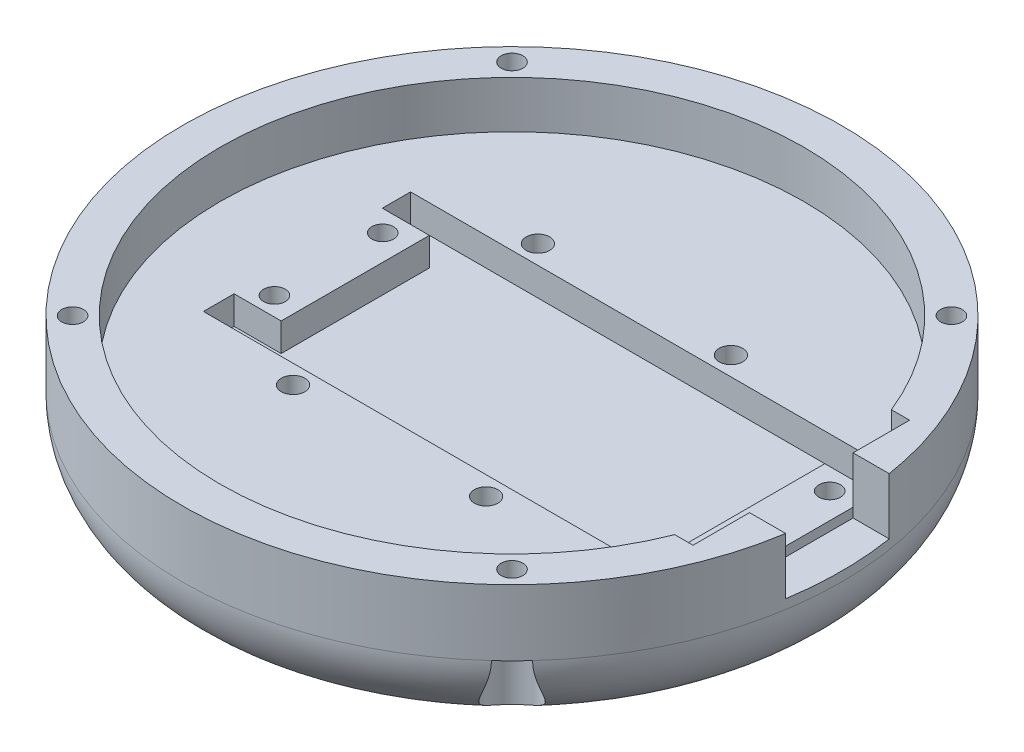
SolidWorks part; units mm, degrees
ref_plane "Front Plane" through (0, 0, 0) normal (0, 0, 1) x (1, 0, 0)
ref_plane "Top Plane" through (0, 0, 0) normal (0, 1, 0) x (1, 0, 0)
ref_plane "Right Plane" through (0, 0, 0) normal (1, 0, 0) x (0, 0, -1)
sketch "Sketch1" plane through (0, 0, 0) normal (0, 1, 0) x (1, 0, 0)
  circle A0 centre (0, 0) radius 35
  dimension "D1" = 70
extrude "Boss-Extrude1" add sketch "Sketch1" along normal blind 10
sketch "Sketch2" plane through (0, 10, 0) normal (0, 1, 0) x (1, 0, 0)
  line L0 (0, 0) -> (35, 0) construction
  line L1 (-21.7735, -11) -> (-21.7735, 11)
  line L2 (-21.7735, -11) -> (30.2265, -11)
  line L3 (-21.7735, 11) -> (30.2265, 11)
  line L4 (30.2265, -11) -> (30.2265, 11)
  line L5 (-21.7735, -11) -> (30.2265, 11) construction
  line L6 (-21.7735, 11) -> (30.2265, -11) construction
  line L7 (30.2265, 11) -> (33.2265, 11) construction
  line L8 (30.2265, 8) -> (25.2265, 8)
  line L9 (25.2265, 8) -> (25.2265, -8)
  line L10 (25.2265, -8) -> (30.2265, -8)
  line L11 (-21.7735, 8) -> (-16.7735, 8)
  line L12 (-16.7735, 8) -> (-16.7735, -7.7436)
  line L13 (-16.7735, -7.7436) -> (-21.7735, -7.7436)
  circle A0 centre (0, 0) radius 35 construction
  circle A1 centre (27.9931, 5.75) radius 1.15
  circle A2 centre (27.9931, -5.75) radius 1.15
  circle A3 centre (-19.4804, -5.75) radius 1.15
  circle A4 centre (-19.4804, 5.75) radius 1.15
  point P7 (4.2265, 0)
  point P28 (0, 0)
  dimension "D3" = 3
  dimension "D7" = 2.3
  dimension "D1" = 52
  dimension "D2" = 22
  dimension "D4" = 3
  dimension "D5" = 3
  dimension "D6" = 5
  dimension "D8" = 11.5
  dimension "D9" = 11.5
  dimension "D10" = 2.25
  dimension "D11" = 2.25
extrude "Cut-Extrude1" cut sketch "Sketch2" against normal blind 3 contours L12 L13 L1 L2 L4 L10 L9 L8 L3 L11 | A3 | A4 | A1 | A2 region at (4.1959, 10, 0.0102) region at (27.9931, 10, -5.75) region at (27.9931, 10, 5.75) region at (-19.4804, 10, 5.75) region at (-19.4804, 10, -5.75)
sketch "Sketch3" plane through (0, 10, 0) normal (0, 1, 0) x (1, 0, 0)
  line L0 (30.7265, 11.5) -> (30.7265, 5.5)
  line L1 (30.7265, -11.5) -> (28.788, -11.5)
  line L2 (30.7265, 11.5) -> (28.788, 11.5)
  line L3 (30.7265, 5.5) -> (34.5652, 5.5)
  line L4 (30.7265, -5.5) -> (34.5652, -5.5)
  line L5 (-21.7735, 11) -> (30.2265, 11) construction
  line L6 (-21.7735, -11) -> (30.2265, -11) construction
  line L7 (30.2265, -11) -> (30.2265, -8) construction
  line L8 (30.7265, -5.5) -> (30.7265, -11.5)
  arc A0 (34.5652, 5.5) -> (34.5652, -5.5) centre (0, 0) ccw
  arc A1 (28.788, 11.5) -> (28.788, -11.5) centre (0, 0) ccw
  dimension "D1" = 4
  dimension "D2" = 70
  dimension "D3" = 0.5
  dimension "D4" = 0.5
  dimension "D5" = 0.5
  dimension "D6" = 11
  dimension "D7" = 5.5
extrude "Boss-Extrude2" add sketch "Sketch3" along normal blind 5
sketch "Sketch12" plane through (0, 0, 0) normal (0, -1, 0) x (1, 0, 0)
  line L0 (-23.3345, 23.3345) -> (0, 0) construction
  line L1 (0, 0) -> (-29.7292, 0) construction
  circle A0 centre (-23.3345, 23.3345) radius 1.15
  circle A1 centre (23.3345, 23.3345) radius 1.15
  circle A2 centre (23.3345, -23.3345) radius 1.15
  circle A3 centre (-23.3345, -23.3345) radius 1.15
  point P14 (0, 0)
  dimension "D3" = 2.3
  dimension "D1" = 33
  dimension "D2" = 45
  dimension "D4" = 4
extrude "Cut-Extrude3" cut sketch "Sketch12" against normal through all both and the other way through all
sketch "Sketch13" plane through (0, 0, 0) normal (0, -1, 0) x (1, 0, 0)
  circle A0 centre (-23.3345, 23.3345) radius 2.5
  circle A1 centre (23.3345, 23.3345) radius 2.5
  circle A2 centre (23.3345, -23.3345) radius 2.5
  circle A3 centre (-23.3345, -23.3345) radius 2.5
  point P12 (0, 0)
  dimension "D1" = 5
  dimension "D2" = 4
extrude "Cut-Extrude4" cut sketch "Sketch13" against normal blind 8
fillet "Fillet2" radius 8 1 edges at (0, 0, 35)
sketch "Sketch14" plane through (0, 0, 0) normal (0, -1, 0) x (1, 0, 0)
  circle A0 centre (0, 0) radius 22.5
  dimension "D1" = 45
extrude "Cut-Extrude5" cut sketch "Sketch14" against normal blind 2
sketch "Sketch15" plane through (0, 10, 0) normal (0, 1, 0) x (1, 0, 0)
  line L0 (-10.25, -11.75) -> (-10.25, 11.75)
  line L1 (-9, -13) -> (9, -13)
  line L2 (-9, 13) -> (9, 13)
  line L3 (10.25, -11.75) -> (10.25, 11.75)
  line L4 (-9.4761, -12.0184) -> (9.4761, 12.0184) construction
  line L5 (-9.4761, 12.0184) -> (9.4761, -12.0184) construction
  circle A0 centre (-10.25, 13) radius 1.25
  circle A1 centre (10.25, 13) radius 1.25
  circle A2 centre (-10.25, -13) radius 1.25
  circle A3 centre (10.25, -13) radius 1.25
  point P1 (0, 0)
  dimension "D3" = 2.5
  dimension "D1" = 20.5
  dimension "D2" = 26
extrude "Cut-Extrude6" cut sketch "Sketch15" against normal blind 6 contours A0 | A2 | A1 | A3 region at (-10.25, 10, 13) region at (-10.25, 10, -13) region at (10.25, 10, -13)
sketch "Sketch16" plane through (0, 10, 0) normal (0, 1, 0) x (1, 0, 0)
  line L0 (34.5652, -5.5) -> (30.7265, -5.5) construction
  line L1 (30.7265, 5.5) -> (37.0915, 5.5)
  line L2 (30.7265, 5.5) -> (30.7265, -5.5)
  line L3 (30.7265, -5.5) -> (37.0915, -5.5)
  line L4 (37.0915, 5.5) -> (37.0915, -5.5)
extrude "Cut-Extrude7" cut sketch "Sketch16" against normal blind 1
